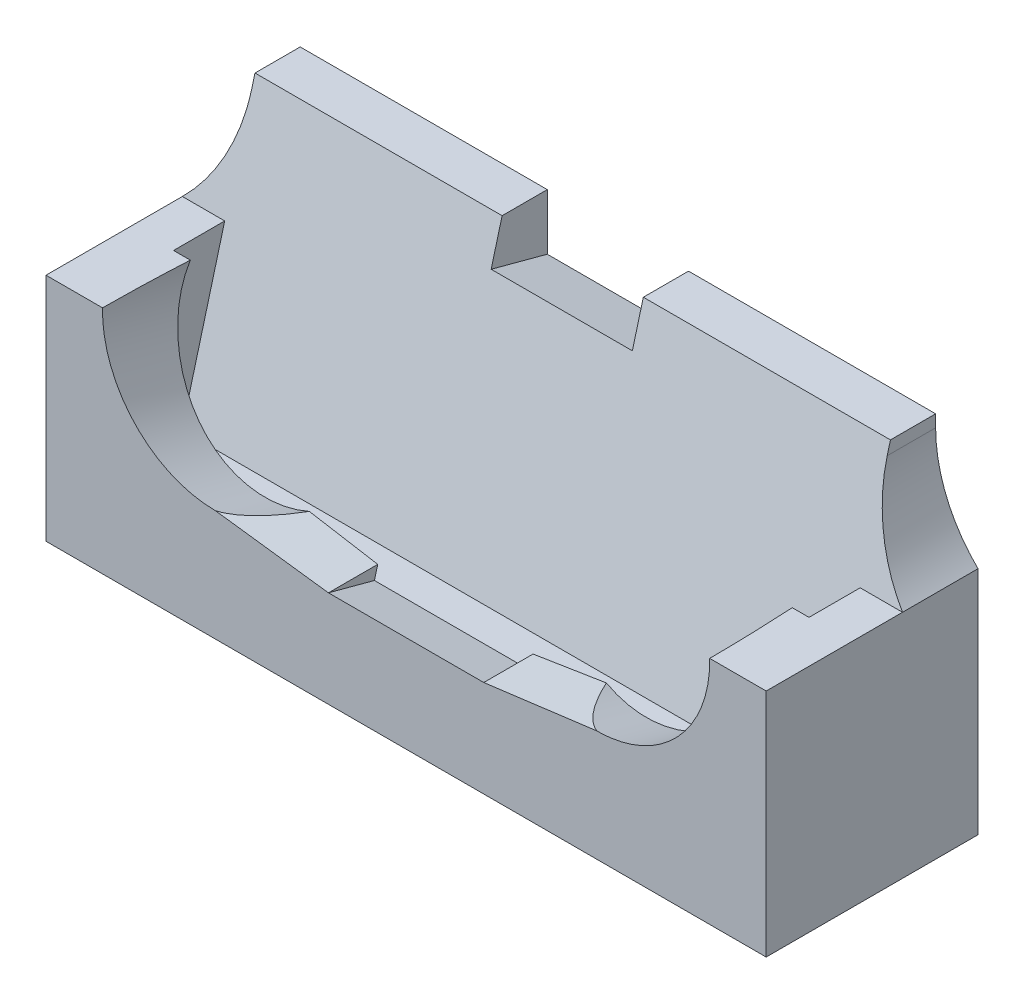
SolidWorks part; units mm, degrees
ref_plane "Front Plane" through (0, 0, 0) normal (0, 0, 1) x (1, 0, 0)
ref_plane "Top Plane" through (0, 0, 0) normal (0, 1, 0) x (1, 0, 0)
ref_plane "Right Plane" through (0, 0, 0) normal (1, 0, 0) x (0, 0, -1)
sketch "Sketch1" plane through (0, 0, 0) normal (0, 1, 0) x (1, 0, 0)
  line L1 (-21.375, 9.5455) -> (23.625, 9.5455)
  line L2 (-21.375, 9.5455) -> (-21.375, -5.4545)
  line L3 (-21.375, -5.4545) -> (23.625, -5.4545)
  line L4 (23.625, 9.5455) -> (23.625, -5.4545)
  dimension "D1" = 45
  dimension "D2" = 15
extrude "Boss-Extrude1" add sketch "Sketch1" along normal blind 5
sketch "Sketch2" plane through (23.625, 0, 0) normal (1, 0, 0) x (0, 0, -1)
  line L0 (-2.4545, 5) -> (2.7218, 24.3185)
  line L1 (-5.4545, 5) -> (9.5455, 5) construction
  line L2 (1.1689, 5) -> (6.3453, 24.3185)
  line L4 (9.5455, 5) -> (1.1689, 5)
  line L5 (-2.4545, 5) -> (-5.4545, 5)
  line L6 (-5.4545, 5) -> (-5.4545, 24.3185)
  line L7 (-5.4545, 24.3185) -> (2.7218, 24.3185)
  line L8 (9.5455, 5) -> (9.5455, 24.3185)
  line L9 (9.5455, 24.3185) -> (6.3453, 24.3185)
  dimension "D1" = 3.5
  dimension "D2" = 20
  dimension "D3" = 20
  dimension "D4" = 75
  dimension "D5" = 3
extrude "Boss-Extrude2" add sketch "Sketch2" against normal up to vertex (45 mm away) up to point (-21.375, 5, 5.4545)
sketch "Sketch5" plane through (0, 0.9486, 3.5401) normal (0, -0.2588, -0.9659) x (-1, 0, 0)
  line L0 (-14.625, 6.1943) -> (12.375, 6.1943)
  line L1 (21.375, 4.1943) -> (-23.625, 4.1943) construction
  line L2 (-23.625, 4.1943) -> (-23.625, 24.1943) construction
  circle A0 centre (-14.625, 14.1943) radius 8
  circle A1 centre (12.375, 14.1943) radius 8
  dimension "D1" = 16
  dimension "D2" = 16
  dimension "D3" = 27
  dimension "D4" = 2
  dimension "D5" = 9
extrude "Cut-Extrude1" cut sketch "Sketch5" against normal blind 10 contours A1 | A0 region at (-12.375, 14.6593, -0.1336) region at (14.625, 14.6593, -0.1336)
sketch "Sketch6" plane through (0, 0, 5.4545) normal (0, 0, 1) x (1, 0, 0)
  line L0 (23.625, 24.3185) -> (23.625, 0) construction
  line L1 (-21.375, 24.3185) -> (23.625, 24.3185)
  line L2 (-21.375, 24.3185) -> (-21.375, 16.3185)
  line L3 (-21.375, 16.3185) -> (23.625, 16.3185)
  line L4 (23.625, 24.3185) -> (23.625, 16.3185)
  point P5 (23.625, 16.1566)
  dimension "D1" = 8
extrude "Cut-Extrude2" cut sketch "Sketch6" against normal up to surface (8.1764 mm away) up to face at (-12.375, 22.3867, -2.2042)
sketch "Sketch7" plane through (0, 0.9486, 3.5401) normal (0, -0.2588, -0.9659) x (-1, 0, 0)
  line L1 (-6.625, 5.1943) -> (4.375, 5.1943)
  line L2 (-6.625, 5.1943) -> (-6.625, 15.9121)
  line L3 (-6.625, 15.9121) -> (4.375, 15.9121)
  line L4 (4.375, 5.1943) -> (4.375, 15.9121)
  line L6 (4.5616, 15.9121) -> (-6.8116, 15.9121) construction
  line L7 (21.375, 14.3507) -> (21.375, -1.4117) construction
  line L8 (21.375, 4.1943) -> (-23.625, 4.1943) construction
  dimension "D1" = 11
  dimension "D2" = 0
  dimension "D3" = 17
  dimension "D4" = 1
extrude "Cut-Extrude4" cut sketch "Sketch7" against normal blind 6.5
sketch "Sketch9" plane through (0, 0, 5.4545) normal (0, 0, 1) x (1, 0, 0)
  line L0 (-12.375, 7.8744) -> (-4.375, 6.8391)
  line L1 (6.625, 6.8391) -> (14.625, 7.8744)
  line L2 (6.625, 6.8391) -> (-4.375, 6.8391)
  line L3 (-12.375, 7.8744) -> (-12.375, 17.1427)
  line L4 (-12.375, 17.1427) -> (14.625, 17.1427)
  line L5 (14.625, 7.8744) -> (14.625, 17.1427)
  ellipse E0 centre (-12.375, 16.1566) end of major axis (-12.375, 7.8744) minor radius 8 (-20.3735, 16.3185) -> (-4.375, 16.1566) ccw construction
  ellipse E1 centre (14.625, 16.1566) end of major axis (14.625, 7.8744) minor radius 8 (6.625, 16.1566) -> (22.6235, 16.3185) ccw construction
extrude "Cut-Extrude5" cut sketch "Sketch9" against normal up to surface (3.7702 mm away) up to face at (1.125, 9.9501, 1.1282)
sketch "Sketch10" plane through (-21.375, 0, 0) normal (-1, 0, 0) x (0, 0, 1)
  line L1 (5.4545, 16.3185) -> (-9.5455, 16.3185)
  line L2 (5.4545, 16.3185) -> (5.4545, 0)
  line L3 (5.4545, 0) -> (-9.5455, 0)
  line L4 (-9.5455, 16.3185) -> (-9.5455, 0)
  point P5 (-9.5455, 0)
extrude "Boss-Extrude3" add sketch "Sketch10" along normal blind 3
sketch "Sketch11" plane through (23.625, 0, 0) normal (1, 0, 0) x (0, 0, -1)
  line L0 (9.5455, 24.3185) -> (9.5455, 0) construction
  line L1 (-5.4545, 16.3185) -> (9.5455, 16.3185)
  line L2 (-5.4545, 16.3185) -> (-5.4545, 0)
  line L3 (-5.4545, 0) -> (9.5455, 0)
  line L4 (9.5455, 16.3185) -> (9.5455, 0)
  line L5 (-5.4545, 0) -> (9.5455, 0) construction
  point P7 (-5.4545, 0)
extrude "Boss-Extrude4" add sketch "Sketch11" along normal blind 3
sketch "Sketch12" plane through (0, 0.0427, 0.1594) normal (0, 0.2588, 0.9659) x (1, 0, 0)
  line L0 (-21.375, 5.1322) -> (23.625, 5.1322) construction
  line L1 (-3.875, 29.8114) -> (6.125, 29.8114)
  line L2 (-3.875, 29.8114) -> (-3.875, 22.1322)
  line L3 (-3.875, 22.1322) -> (6.125, 22.1322)
  line L4 (6.125, 29.8114) -> (6.125, 22.1322)
  line L5 (23.625, 25.1322) -> (23.625, 16.85) construction
  line L6 (-21.375, 25.1322) -> (-21.375, 16.85) construction
  dimension "D1" = 10
  dimension "D2" = 17
  dimension "D3" = 17.5
  dimension "D4" = 17.5
extrude "Cut-Extrude6" cut sketch "Sketch12" against normal blind 6
fillet "Fillet1" radius 10 2 edges at (-21.375, 16.3185, -6.8736) (23.625, 16.3185, -6.8736)
